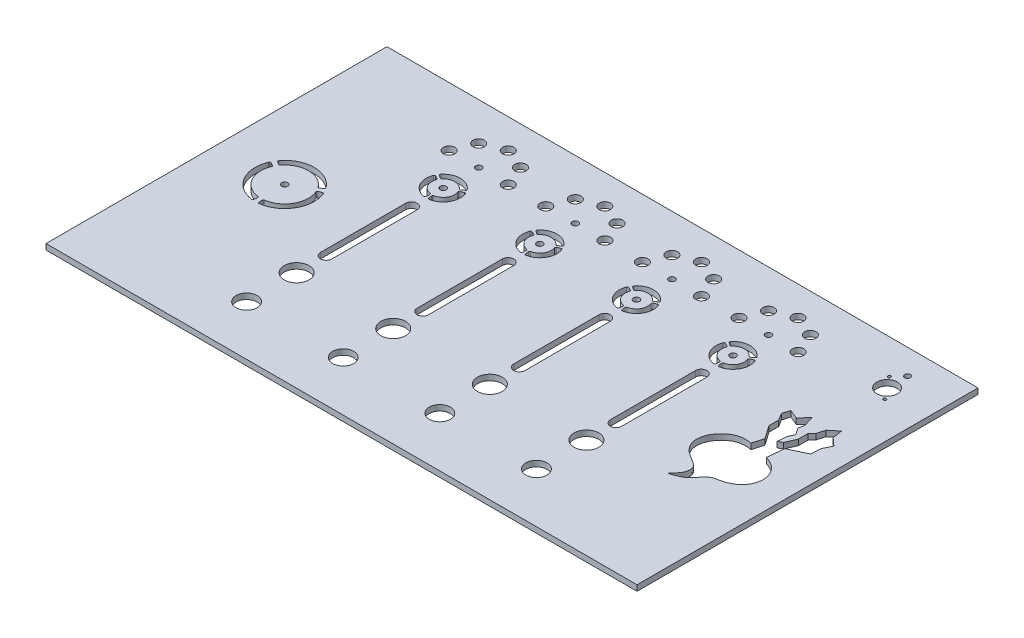
SolidWorks part; units mm, degrees
ref_plane "Front Plane" through (0, 0, 0) normal (0, 0, 1) x (1, 0, 0)
ref_plane "Top Plane" through (0, 0, 0) normal (0, 1, 0) x (1, 0, 0)
ref_plane "Right Plane" through (0, 0, 0) normal (1, 0, 0) x (0, 0, -1)
sketch "Sketch1" plane through (0, 0, 0) normal (0, 1, 0) x (1, 0, 0)
  line L1 (-330.2, 190.5) -> (330.2, 190.5)
  line L2 (-330.2, 190.5) -> (-330.2, -190.5)
  line L3 (-330.2, -190.5) -> (330.2, -190.5)
  line L4 (330.2, 190.5) -> (330.2, -190.5)
  line L5 (-330.2, 190.5) -> (330.2, -190.5) construction
  line L6 (-330.2, -190.5) -> (330.2, 190.5) construction
  point P0 (0, 0)
  dimension "D1" = 660.4
  dimension "D2" = 381
extrude "Boss-Extrude1" add sketch "Sketch1" along normal blind 6.35
sketch "Sketch2" plane through (0, 6.35, 0) normal (0, 1, 0) x (1, 0, 0)
  line L0 (-161.925, 49.53) -> (-161.925, -45.72) construction
  line L1 (-155.575, 49.53) -> (-155.575, -45.72)
  line L2 (-168.275, 49.53) -> (-168.275, -45.72)
  line L3 (-330.2, -190.5) -> (330.2, -190.5) construction
  line L4 (-330.2, 190.5) -> (-330.2, -190.5) construction
  circle A0 centre (-161.925, -134.62) radius 11.811
  circle A1 centre (-161.925, -78.74) radius 13.843
  circle A2 centre (-161.925, 85.09) radius 3.429
  circle A3 centre (-161.925, 124.714) radius 3.429
  circle A4 centre (-194.945, 124.714) radius 6.35
  circle A5 centre (-185.2737, 148.0627) radius 6.35
  circle A6 centre (-161.925, 157.734) radius 6.35
  circle A7 centre (-138.5763, 148.0627) radius 6.35
  circle A8 centre (-128.905, 124.714) radius 6.35
  arc A9 (-155.575, 49.53) -> (-168.275, 49.53) centre (-161.925, 49.53) ccw
  arc A10 (-168.275, -45.72) -> (-155.575, -45.72) centre (-161.925, -45.72) ccw
  circle A11 centre (-161.925, 124.714) radius 3.429
  circle A12 centre (-161.925, 124.714) radius 3.429
  circle A13 centre (-161.925, 124.714) radius 3.429
  circle A14 centre (-161.925, 124.714) radius 3.429
  circle A15 centre (-170.561, 130.556) radius 1.397
  circle A16 centre (-170.561, 113.792) radius 1.397
  circle A17 centre (-161.925, 85.09) radius 19.05
  circle A18 centre (-161.925, 124.714) radius 8.89
  circle A19 centre (-161.925, 85.09) radius 8.89
  circle A20 centre (-161.925, -134.62) radius 30.099
  circle A21 centre (-161.925, -78.74) radius 16.637
  point P11 (-161.925, 1.905)
  point P20 (-161.925, 124.714)
  dimension "D2" = 23.622
  dimension "D3" = 27.686
  dimension "D4" = 12.7
  dimension "D7" = 6.858
  dimension "D8" = 6.858
  dimension "D9" = 2.794
  dimension "D10" = 16.764
  dimension "D19" = 38.1
  dimension "D20" = 17.78
  dimension "D21" = 17.78
  dimension "D17" = 33.02
  dimension "D23" = 60.198
  dimension "D24" = 33.274
  dimension "D5" = 95.25
  dimension "D6" = 12.7
  dimension "D11" = 8.636
  dimension "D12" = 5.842
  dimension "D13" = 33.02
  dimension "D14" = 55.88
  dimension "D15" = 168.275
  dimension "D16" = 55.88
  dimension "D18" = 35.56
  dimension "D22" = 39.624
  dimension "D1" = 5
extrude "Cut-Extrude1" cut sketch "Sketch2" against normal through all contours L2 A10 L1 A9 | A2 | A5 | A6 | A7 | A8 | A0 | A1 | A3 | A4 region at (-161.925, 6.35, -1.905) region at (-161.925, 6.35, 134.62) region at (-161.925, 6.35, 78.74) region at (-161.925, 6.35, -85.09) region at (-161.925, 6.35, -124.714) region at (-194.945, 6.35, -124.714) region at (-185.2737, 6.35, -148.0627) region at (-161.925, 6.35, -157.734) region at (-138.5763, 6.35, -148.0627) region at (-128.905, 6.35, -124.714)
sketch "Sketch10" plane through (0, 6.35, 0) normal (0, 1, 0) x (1, 0, 0)
  line L0 (-161.925, 85.09) -> (-177.5298, 96.0166) construction
  line L1 (-161.925, 85.09) -> (-146.3202, 96.0166) construction
  line L2 (-176.4523, 95.2621) -> (-173.3212, 93.0697)
  line L3 (-150.5288, 93.0697) -> (-147.3977, 95.2621)
  line L4 (-145.852, 92.585) -> (-149.3163, 90.9695)
  line L5 (-160.7125, 71.2308) -> (-160.3793, 67.4229)
  line L6 (-163.4707, 67.4229) -> (-163.1375, 71.2308)
  line L7 (-174.5337, 90.9695) -> (-177.998, 92.585)
  arc A0 (-171.6229, 93.29) -> (-152.2271, 93.29) centre (-161.925, 85.09) cw
  arc A1 (-176.7095, 97.1034) -> (-147.1405, 97.1034) centre (-161.925, 85.09) cw
  arc A2 (-176.4523, 95.2621) -> (-176.7095, 97.1034) centre (-175.7239, 96.3025) cw
  arc A3 (-150.5288, 93.0697) -> (-152.2271, 93.29) centre (-151.2573, 94.11) cw
  arc A4 (-147.3977, 95.2621) -> (-147.1405, 97.1034) centre (-148.1261, 96.3025) ccw
  arc A5 (-171.6229, 93.29) -> (-173.3212, 93.0697) centre (-172.5927, 94.11) cw
  arc A6 (-144.1289, 91.8871) -> (-158.9134, 66.2796) centre (-161.925, 85.09) cw
  arc A7 (-145.852, 92.585) -> (-144.1289, 91.8871) centre (-145.3153, 91.4339) cw
  arc A8 (-149.9746, 89.3887) -> (-159.6726, 72.5913) centre (-161.925, 85.09) cw
  arc A9 (-149.9746, 89.3887) -> (-149.3163, 90.9695) centre (-148.7796, 89.8185) cw
  arc A10 (-160.7125, 71.2308) -> (-159.6726, 72.5913) centre (-159.4473, 71.3415) cw
  arc A11 (-160.3793, 67.4229) -> (-158.9134, 66.2796) centre (-159.1142, 67.5336) ccw
  arc A12 (-164.9366, 66.2796) -> (-179.7211, 91.8871) centre (-161.925, 85.09) cw
  arc A13 (-163.4707, 67.4229) -> (-164.9366, 66.2796) centre (-164.7358, 67.5336) cw
  arc A14 (-164.1774, 72.5913) -> (-173.8754, 89.3887) centre (-161.925, 85.09) cw
  arc A15 (-164.1774, 72.5913) -> (-163.1375, 71.2308) centre (-164.4027, 71.3415) cw
  arc A16 (-174.5337, 90.9695) -> (-173.8754, 89.3887) centre (-175.0704, 89.8185) cw
  arc A17 (-177.998, 92.585) -> (-179.7211, 91.8871) centre (-178.5347, 91.4339) ccw
  point P11 (-151.5218, 92.3744)
  point P17 (-172.3282, 92.3744)
  point P44 (-161.925, 85.09)
  dimension "D2" = 12.7
  dimension "D3" = 19.05
  dimension "D4" = 1.27
  dimension "D1" = 110
  dimension "D5" = 3
extrude "Cut-Extrude9" cut sketch "Sketch10" against normal through all
pattern_linear "LPattern1" count 4 spacing 107.95 along (1, 0, 0) of "Cut-Extrude1", "Cut-Extrude9"
sketch "Sketch5" plane through (0, 6.35, 0) normal (0, 1, 0) x (1, 0, 0)
  line L0 (-281.0484, 18.9395) -> (-254, 0) construction
  line L1 (-254, 0) -> (-226.9516, 18.9395) construction
  line L2 (-254, 0) -> (-254, 46.9935) construction
  line L3 (-279.9873, 18.1965) -> (-276.8635, 16.0092)
  line L4 (-231.1365, 16.0092) -> (-228.0127, 18.1965)
  line L5 (-225.2478, 13.4074) -> (-228.7039, 11.7957)
  line L6 (-251.5674, -27.8049) -> (-251.235, -31.6039)
  line L7 (-256.765, -31.6039) -> (-256.4326, -27.8049)
  line L8 (-279.2961, 11.7957) -> (-282.7522, 13.4074)
  line L9 (-330.2, 190.5) -> (-330.2, -190.5) construction
  circle A0 centre (-254, 0) radius 3.429
  circle A1 centre (-254, 0) radius 17.78
  arc A2 (-223.5395, 12.7466) -> (-249.8086, -32.7529) centre (-254, 0) cw
  arc A3 (-275.1289, 16.2745) -> (-232.8711, 16.2745) centre (-254, 0) cw
  arc A4 (-280.2692, 20.0063) -> (-227.7308, 20.0063) centre (-254, 0) cw
  arc A5 (-229.3414, 10.1609) -> (-250.4703, -26.4354) centre (-254, 0) cw
  arc A6 (-258.1914, -32.7529) -> (-284.4605, 12.7466) centre (-254, 0) cw
  arc A7 (-257.5297, -26.4354) -> (-278.6586, 10.1609) centre (-254, 0) cw
  arc A8 (-279.2961, 11.7957) -> (-278.6586, 10.1609) centre (-279.8328, 10.6447) cw
  arc A9 (-282.7522, 13.4074) -> (-284.4605, 12.7466) centre (-283.289, 12.2564) ccw
  arc A10 (-258.1914, -32.7529) -> (-256.765, -31.6039) centre (-258.0301, -31.4932) ccw
  arc A11 (-257.5297, -26.4354) -> (-256.4326, -27.8049) centre (-257.6978, -27.6942) cw
  arc A12 (-249.8086, -32.7529) -> (-251.235, -31.6039) centre (-249.9699, -31.4932) cw
  arc A13 (-250.4703, -26.4354) -> (-251.5674, -27.8049) centre (-250.3022, -27.6942) ccw
  arc A14 (-223.5395, 12.7466) -> (-225.2478, 13.4074) centre (-224.711, 12.2564) ccw
  arc A15 (-229.3414, 10.1609) -> (-228.7039, 11.7957) centre (-228.1672, 10.6447) cw
  arc A16 (-231.1365, 16.0092) -> (-232.8711, 16.2745) centre (-231.865, 17.0495) cw
  arc A17 (-228.0127, 18.1965) -> (-227.7308, 20.0063) centre (-228.7412, 19.2368) ccw
  arc A18 (-276.8635, 16.0092) -> (-275.1289, 16.2745) centre (-276.135, 17.0495) ccw
  arc A19 (-279.9873, 18.1965) -> (-280.2692, 20.0063) centre (-279.2588, 19.2368) cw
  point P22 (-254, 0)
  point P29 (-254, 0)
  point P39 (-232.1532, 15.2973)
  point P45 (-275.8468, 15.2973)
  dimension "D1" = 6.858
  dimension "D2" = 35.56
  dimension "D3" = 3
  dimension "D4" = 26.67
  dimension "D5" = 33.02
  dimension "D9" = 1.27
  dimension "D7" = 110
  dimension "D8" = 76.2
  dimension "D6" = 3
extrude "Cut-Extrude6" cut sketch "Sketch5" against normal through all contours A0 | L3 A3 L4 | L7 A7 L8 | L5 A5 L6 region at (-279.9625, 6.35, -19.1272) region at (-224.453, 6.35, -12.9234) region at (-257.5815, 6.35, 32.0501) region at (-254, 6.35, 0)
sketch "Sketch6" plane through (0, 6.35, 0) normal (0, 1, 0) x (1, 0, 0)
  line L0 (330.2, -190.5) -> (330.2, 190.5) construction
  line L1 (266.7, 154.94) -> (292.1, 154.94)
  line L2 (266.7, 154.94) -> (266.7, 124.46)
  line L3 (266.7, 124.46) -> (292.1, 124.46)
  line L4 (292.1, 154.94) -> (292.1, 124.46)
  line L5 (266.7, 154.94) -> (292.1, 124.46) construction
  line L6 (266.7, 124.46) -> (292.1, 154.94) construction
  line L7 (330.2, 190.5) -> (-330.2, 190.5) construction
  circle A0 centre (279.4, 139.7) radius 11.43
  circle A1 centre (279.4, 162.56) radius 3.175
  circle A2 centre (269.748, 151.892) radius 1.651
  circle A3 centre (289.052, 127.508) radius 1.651
  dimension "D1" = 22.86
  dimension "D2" = 6.35
  dimension "D6" = 3.302
  dimension "D9" = 3.048
  dimension "D3" = 22.86
  dimension "D4" = 25.4
  dimension "D5" = 30.48
  dimension "D7" = 3.048
  dimension "D8" = 3.048
  dimension "D10" = 3.048
  dimension "D11" = 50.8
  dimension "D12" = 50.8
extrude "Cut-Extrude7" cut sketch "Sketch6" against normal through all contours A0 | A2 | A3 | A1 region at (279.4, 6.35, -139.7) region at (279.4, 6.35, -162.56) region at (269.748, 6.35, -151.892) region at (289.052, 6.35, -127.508)
sketch "Sketch7" plane through (0, 6.35, 0) normal (0, 1, 0) x (1, 0, 0)
  line L0 (255.7189, 6.2581) -> (260.2157, 22.4284)
  line L1 (260.2157, 22.4284) -> (249.9283, 37.2593)
  line L2 (249.9283, 37.2593) -> (249.9283, 48.0171)
  line L3 (249.9283, 48.0171) -> (245.0916, 55.9581)
  line L4 (245.0916, 55.9581) -> (247.51, 64.1887)
  line L5 (247.51, 64.1887) -> (257.6021, 59.8434)
  line L6 (257.6021, 59.8434) -> (266.331, 69.1607)
  line L7 (266.331, 69.1607) -> (269.778, 56.9273)
  line L8 (270.6732, 37.2593) -> (273.5917, 43.3464)
  line L9 (269.778, 26.5026) -> (274.4256, 29.1709)
  line L10 (274.4256, 29.1709) -> (279.4058, 40.7397)
  line L11 (279.4058, 40.7397) -> (279.4058, 51.0798)
  line L12 (279.4058, 51.0798) -> (283.6828, 55.9581)
  line L13 (283.6828, 55.9581) -> (286.2797, 64.796)
  line L14 (286.2797, 64.796) -> (295.7541, 72.4954)
  line L15 (295.7541, 72.4954) -> (297.3234, 61.5107)
  line L16 (297.3234, 61.5107) -> (305.9452, 53.6862)
  line L17 (305.9452, 53.6862) -> (301.2757, 43.9301)
  line L18 (301.2757, 43.9301) -> (300.4876, 32.9233)
  line L19 (300.4876, 32.9233) -> (281.0964, 23.8342)
  line L20 (281.0964, 23.8342) -> (278.9259, 1.7686)
  line L21 (278.9259, 1.7686) -> (255.7189, 6.2581)
  line L22 (269.778, 26.5026) -> (270.6732, 37.2593)
  line L23 (273.5917, 43.3464) -> (268.4218, 51.0798)
  line L24 (268.4218, 51.0798) -> (269.778, 56.9273)
  line L26 (181.5842, 43.0883) -> (224.5474, 43.0883)
  line L27 (181.5842, 43.0883) -> (181.5842, 1.7686)
  line L28 (181.5842, 1.7686) -> (224.5474, 1.7686)
  line L29 (224.5474, 43.0883) -> (224.5474, 1.7686)
  line L30 (181.5842, 43.0883) -> (224.5474, 1.7686) construction
  line L31 (181.5842, 1.7686) -> (224.5474, 43.0883) construction
  spline S0 degree 3 poles (269.8957, 7.0712) (260.2215, 9.4099) (233.6996, 17.3044) (209.0751, -25.3619) (250.4959, -43.3896) (247.3978, -60.0979) (232.6874, -67.8276) (257.5896, -59.8745) (263.392, -45.0431) (297.8507, -40.8718) (303.9159, -14.9658) (285.5677, 5.2291) (269.8957, 7.0712) (260.2215, 9.4099) (233.6996, 17.3044) knots -0.206906 -0.161359 -0.017929 0 0.112637 0.317899 0.358519 0.401499 0.459605 0.498799 0.539957 0.572148 0.793094 0.838641 0.982071 1 1.112637 1.317899 1.358519 only from (263.4579, 8.6384) to (263.4579, 8.6384)
  point P31 (203.0658, 22.4284)
  dimension "D1" = 42.9632
extrude "Cut-Extrude8" cut sketch "Sketch7" against normal through all contours L0 S0 L20 L21 | S0 L20 L19 L18 L17 L16 L15 L14 L13 L12 L11 L10 L9 L22 L8 L23 L24 L7 L6 L5 L4 L3 L2 L1 L0 | L20 S0 L0 L21 region at (259.7999, 6.35, 20.2078) region at (267.3492, 6.35, -5.9094) region at (259.3898, 6.35, -16.0676)
sketch "Sketch11" plane through (0, 6.35, 0) normal (0, 1, 0) x (1, 0, 0)
  line L1 (226.1466, 11.4796) -> (292.1866, 11.4796)
  line L2 (226.1466, 11.4796) -> (226.1466, -54.5604)
  line L3 (226.1466, -54.5604) -> (292.1866, -54.5604)
  line L4 (292.1866, 11.4796) -> (292.1866, -54.5604)
  line L5 (226.1466, 11.4796) -> (292.1866, -54.5604) construction
  line L6 (226.1466, -54.5604) -> (292.1866, 11.4796) construction
  line L7 (257.1608, 63.4896) -> (266.6328, 63.4896)
  line L8 (257.1608, 63.4896) -> (257.1608, 12.6896)
  line L9 (257.1608, 12.6896) -> (266.6328, 12.6896)
  line L10 (266.6328, 63.4896) -> (266.6328, 12.6896)
  line L11 (257.1608, 63.4896) -> (266.6328, 12.6896) construction
  line L12 (257.1608, 12.6896) -> (266.6328, 63.4896) construction
  point P0 (259.1666, -21.5404)
  point P5 (261.8968, 38.231)
  point P7 (261.8968, 38.0896)
  dimension "D1" = 66.04
  dimension "D2" = 66.04
  dimension "D3" = 50.8
